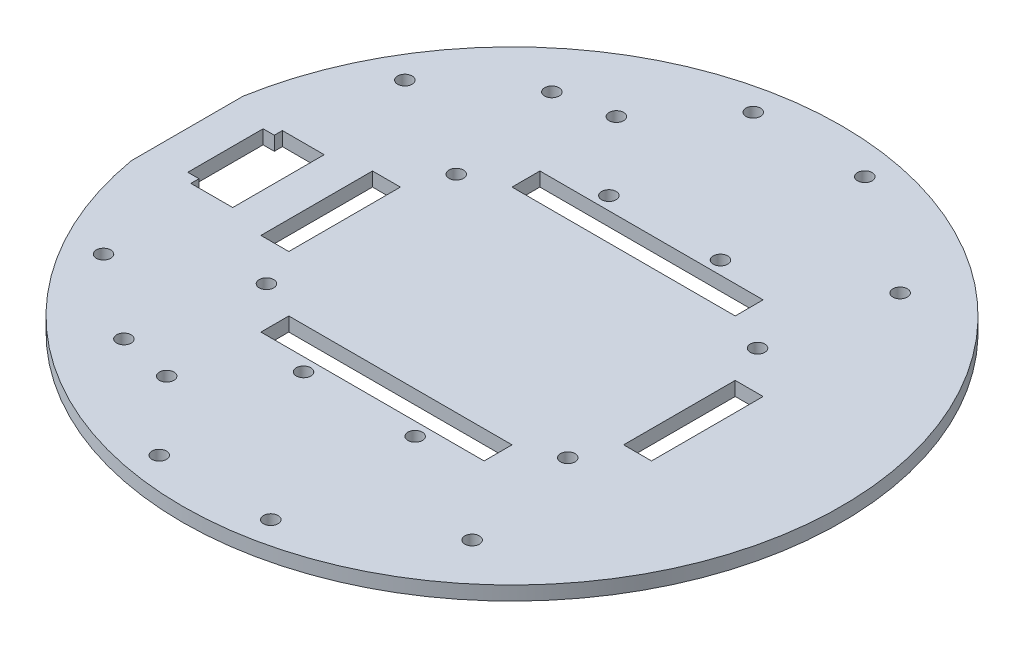
SolidWorks part; units mm, degrees
material "Acrylic (Medium-high impact)"
ref_plane "Front Plane" through (0, 0, 0) normal (0, 0, 1) x (1, 0, 0)
ref_plane "Top Plane" through (0, 0, 0) normal (0, 1, 0) x (1, 0, 0)
ref_plane "Right Plane" through (0, 0, 0) normal (1, 0, 0) x (0, 0, -1)
sketch "Sketch1" plane through (0, 0, 0) normal (0, 1, 0) x (1, 0, 0)
  line L0 (-73.9169, 12.7) -> (-73.9169, -12.7)
  line L1 (-73.9169, 12.7) -> (-73.9169, -12.7) construction
  line L2 (-34.29, 21.59) -> (34.29, 21.59) construction
  line L3 (34.29, 21.59) -> (34.29, -21.59) construction
  line L4 (34.29, -21.59) -> (-34.29, -21.59) construction
  line L5 (-34.29, -21.59) -> (-34.29, 21.59) construction
  line L6 (0, 21.59) -> (0, 75) construction
  line L7 (34.29, 0) -> (75, 0) construction
  line L8 (0, -25.4) -> (0, -21.59) construction
  line L9 (-34.29, 0) -> (-38.1, 0) construction
  line L10 (-25.4, 31.75) -> (25.4, 31.75)
  line L11 (-25.4, 31.75) -> (-25.4, 25.4)
  line L12 (-25.4, 25.4) -> (25.4, 25.4)
  line L13 (25.4, 31.75) -> (25.4, 25.4)
  line L14 (38.1, 12.7) -> (44.45, 12.7)
  line L15 (38.1, 12.7) -> (38.1, -12.7)
  line L16 (38.1, -12.7) -> (44.45, -12.7)
  line L17 (44.45, 12.7) -> (44.45, -12.7)
  line L18 (25.4, -25.4) -> (-25.4, -25.4)
  line L19 (25.4, -25.4) -> (25.4, -31.75)
  line L20 (25.4, -31.75) -> (-25.4, -31.75)
  line L21 (-25.4, -25.4) -> (-25.4, -31.75)
  line L22 (-44.45, -12.7) -> (-38.1, -12.7)
  line L23 (-44.45, -12.7) -> (-44.45, 12.7)
  line L24 (-44.45, 12.7) -> (-38.1, 12.7)
  line L25 (-38.1, -12.7) -> (-38.1, 12.7)
  line L26 (38.1, 12.7) -> (34.29, 12.7) construction
  line L27 (25.4, 25.4) -> (25.4, 21.59) construction
  line L28 (-24.25, -37.9184) -> (24.25, -37.9184) construction
  line L29 (24.25, -37.9184) -> (24.25, -64.4184) construction
  line L30 (-12.7, -37.9184) -> (-12.7, -34.7434) construction
  line L31 (24.25, -64.4184) -> (-24.25, -64.4184) construction
  line L32 (-24.25, -64.4184) -> (-24.25, -37.9184) construction
  line L33 (-24.25, -64.4184) -> (-26.4232, -70.1913) construction
  line L34 (24.25, -64.4184) -> (26.4232, -70.1913) construction
  line L35 (-24.25, -37.9184) -> (-24.25, -31.75) construction
  line L36 (0, -37.9184) -> (0, -64.4184) construction
  line L37 (-53.151, 0) -> (-44.45, 0) construction
  line L38 (-27.425, -51.1684) -> (-24.25, -51.1684) construction
  line L39 (-12.7, -67.5934) -> (-12.7, -64.4184) construction
  line L40 (-65.216, 8.5725) -> (-62.676, 8.5725)
  line L41 (-65.216, 8.5725) -> (-65.216, -8.5725)
  line L42 (-65.216, -8.5725) -> (-62.676, -8.5725)
  line L43 (-53.151, 8.5725) -> (-53.151, -8.5725)
  line L44 (-62.676, 8.5725) -> (-62.676, 10.414)
  line L45 (-62.676, 10.414) -> (-53.151, 10.414)
  line L46 (-53.151, 10.414) -> (-53.151, 8.5725)
  line L47 (-62.676, -8.5725) -> (-62.676, -10.414)
  line L48 (-62.676, -10.414) -> (-53.151, -10.414)
  line L49 (-53.151, -10.414) -> (-53.151, -8.5725)
  line L50 (-65.216, 0) -> (-73.9169, 0) construction
  line L51 (55.1757, 50.8) -> (55.1757, -50.8) construction
  arc A0 (-73.9169, -12.7) -> (-73.9169, 12.7) centre (0, 0) ccw
  arc A1 (55.356, -50.6035) -> (55.356, 50.6035) centre (0, 0) ccw construction
  circle A2 centre (-34.29, 21.59) radius 1.651
  circle A3 centre (34.29, 21.59) radius 1.651
  circle A4 centre (-34.29, -21.59) radius 1.651
  circle A5 centre (34.29, -21.59) radius 1.651
  circle A6 centre (-39.6269, 48.6985) radius 1.651 construction
  circle A7 centre (39.6269, -48.6985) radius 1.651
  circle A8 centre (-39.6269, -48.6985) radius 1.651
  circle A9 centre (-58.6769, -34.29) radius 1.651
  circle A10 centre (-58.6769, 34.29) radius 1.651
  circle A11 centre (-39.6269, 48.6985) radius 1.651
  circle A12 centre (39.6269, 48.6985) radius 1.651
  circle A13 centre (39.6269, -48.6985) radius 1.651 construction
  circle A14 centre (12.7, -67.5934) radius 1.651
  circle A15 centre (12.7, -34.7434) radius 1.651
  circle A16 centre (12.7, 34.7434) radius 1.651
  circle A17 centre (12.7, 67.5934) radius 1.651
  circle A22 centre (-27.425, -51.1684) radius 1.651
  circle A23 centre (-12.7, -34.7434) radius 1.651
  circle A24 centre (-12.7, -67.5934) radius 1.651
  circle A25 centre (-12.7, 67.5934) radius 1.651
  circle A26 centre (-27.425, 51.1684) radius 1.651
  circle A27 centre (-12.7, 34.7434) radius 1.651
  dimension "D11" = 3.302
  dimension "D1" = 68.58
  dimension "D2" = 43.18
  dimension "D3" = 3.81
  dimension "D4" = 6.35
  dimension "D5" = 50.8
  dimension "D6" = 25.4
  dimension "D7" = 48.5
  dimension "D8" = 26.5
  dimension "D9" = 12.7
  dimension "D10" = 3.175
  dimension "D12" = 17.145
  dimension "D13" = 12.065
  dimension "D14" = 101.6
  dimension "D15" = 2.54
  dimension "D16" = 20.828
  dimension "D17" = 9.525
extrude "Boss-Extrude1" add sketch "Sketch1" along normal blind 3.175
